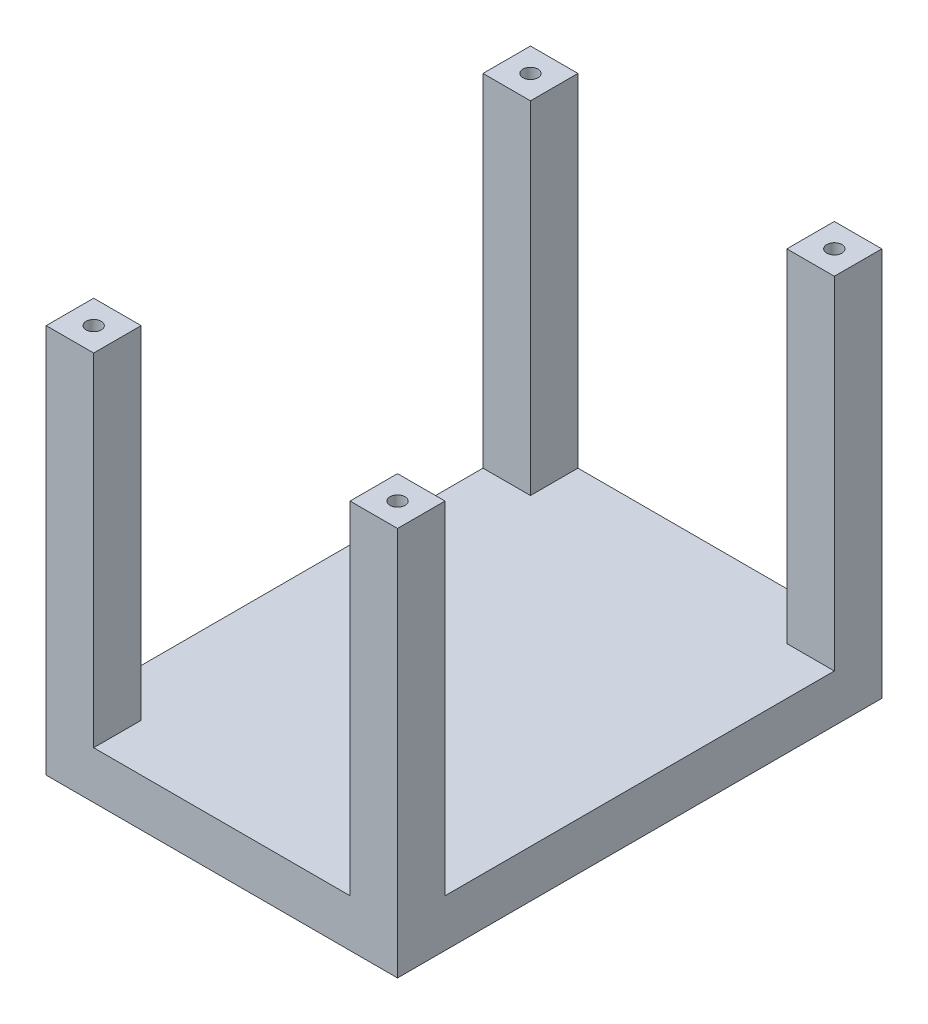
SolidWorks part; units mm, degrees
ref_plane "Alzado" through (0, 0, 0) normal (0, 0, 1) x (1, 0, 0)
ref_plane "Planta" through (0, 0, 0) normal (0, 1, 0) x (1, 0, 0)
ref_plane "Vista lateral" through (0, 0, 0) normal (1, 0, 0) x (0, 0, -1)
sketch "Croquis1" plane through (0, 0, 0) normal (0, 1, 0) x (1, 0, 0)
  line L1 (-21.0659, 11.644) -> (-16.0659, 11.644)
  line L2 (-21.0659, 11.644) -> (-21.0659, 6.644)
  line L3 (-21.0659, 6.644) -> (-16.0659, 6.644)
  line L4 (-16.0659, 11.644) -> (-16.0659, 6.644)
  line L5 (10.9341, 11.644) -> (15.9341, 11.644)
  line L6 (10.9341, 11.644) -> (10.9341, 6.644)
  line L7 (10.9341, 6.644) -> (15.9341, 6.644)
  line L8 (15.9341, 11.644) -> (15.9341, 6.644)
  line L9 (-21.0659, -34.356) -> (-16.0659, -34.356)
  line L10 (-21.0659, -34.356) -> (-21.0659, -39.356)
  line L11 (-21.0659, -39.356) -> (-16.0659, -39.356)
  line L12 (-16.0659, -34.356) -> (-16.0659, -39.356)
  line L13 (10.9341, -34.356) -> (15.9341, -34.356)
  line L14 (10.9341, -34.356) -> (10.9341, -39.356)
  line L15 (10.9341, -39.356) -> (15.9341, -39.356)
  line L16 (15.9341, -34.356) -> (15.9341, -39.356)
  point P17 (-21.0659, 9.144)
  dimension "D1" = 5
  dimension "D2" = 5
  dimension "D3" = 5
  dimension "D4" = 5
  dimension "D5" = 0
  dimension "D6" = 32
  dimension "D7" = 5
  dimension "D8" = 5
  dimension "D9" = 0
  dimension "D10" = 41
  dimension "D11" = 5
  dimension "D12" = 5
  dimension "D13" = 0
  dimension "D14" = 41
extrude "Saliente-Extruir1" add sketch "Croquis1" along normal blind 41
sketch "Croquis2" plane through (0, 0, 0) normal (0, 1, 0) x (1, 0, 0)
  line L1 (-21.0659, 11.644) -> (15.9341, 11.644)
  line L2 (-21.0659, 11.644) -> (-21.0659, -39.356)
  line L3 (-21.0659, -39.356) -> (15.9341, -39.356)
  line L4 (15.9341, 11.644) -> (15.9341, -39.356)
  dimension "D1" = 37
  dimension "D2" = 51
extrude "Saliente-Extruir2" add sketch "Croquis2" along normal blind 5
sketch "Croquis3" plane through (0, 41, 0) normal (0, 1, 0) x (1, 0, 0)
  line L0 (-16.0659, 6.644) -> (-16.0659, 11.644) construction
  line L1 (-16.0659, 11.644) -> (-21.0659, 11.644) construction
  line L4 (-16.0659, -34.356) -> (-16.0659, -39.356) construction
  line L5 (-21.0659, -39.356) -> (-16.0659, -39.356) construction
  line L6 (10.9341, 6.644) -> (10.9341, 11.644) construction
  line L7 (15.9341, 11.644) -> (10.9341, 11.644) construction
  line L8 (10.9341, -34.356) -> (15.9341, -34.356) construction
  line L9 (10.9341, -34.356) -> (10.9341, -39.356) construction
  circle A0 centre (-18.5659, 9.144) radius 0.7937
  circle A1 centre (-18.5659, -36.856) radius 0.7937
  circle A2 centre (13.4341, -36.856) radius 0.7937
  circle A3 centre (13.4341, 9.144) radius 0.7937
  dimension "D1" = 1.5875
  dimension "D4" = 1.5875
  dimension "D9" = 1.5875
  dimension "D10" = 2.5
  dimension "D12" = 1.5875
  dimension "D2" = 2.5
  dimension "D3" = 2.5
  dimension "D5" = 2.5
  dimension "D6" = 2.5
  dimension "D7" = 2.5
  dimension "D8" = 2.5
  dimension "D11" = 2.5
extrude "Cortar-Extruir1" cut sketch "Croquis3" against normal blind 41
